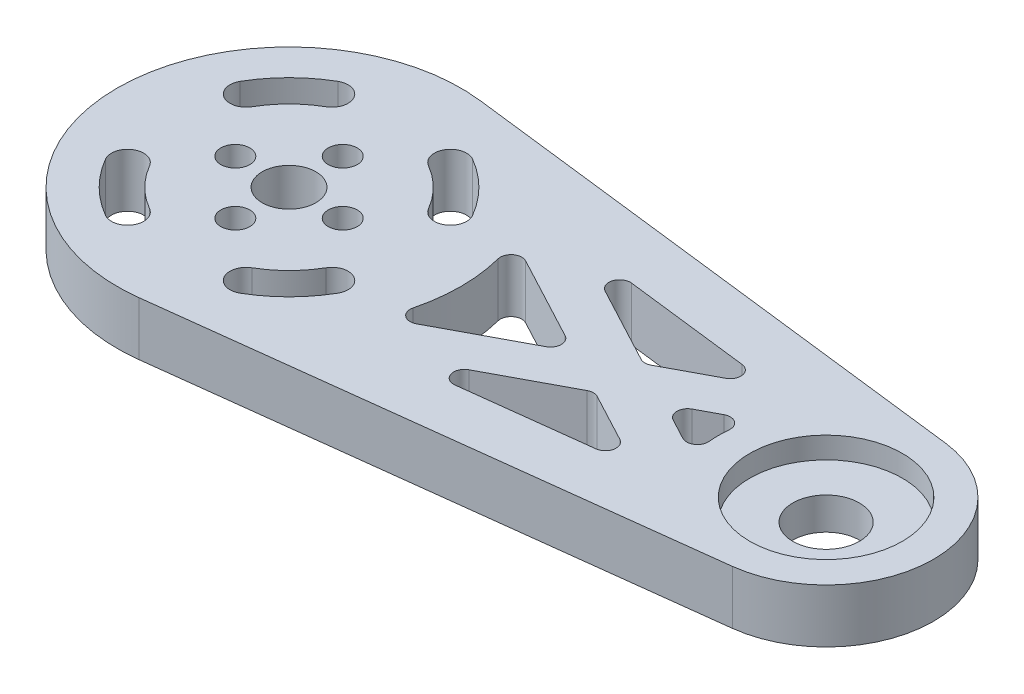
SolidWorks part; units mm, degrees
material "三聚氰胺甲醛树脂"
ref_plane "前视基准面" through (0, 0, 0) normal (0, 0, 1) x (1, 0, 0)
ref_plane "上视基准面" through (0, 0, 0) normal (0, 1, 0) x (1, 0, 0)
ref_plane "右视基准面" through (0, 0, 0) normal (1, 0, 0) x (0, 0, -1)
sketch "草图1" plane through (0, 0, 0) normal (0, 1, 0) x (1, 0, 0)
  line L0 (0, 0) -> (-5.9584, 0) construction
  line L1 (1.92, -15.8844) -> (51.2, -9.9277)
  line L2 (1.92, 15.8844) -> (51.2, 9.9277)
  line L3 (18.3565, 8.8613) -> (38.5355, 6.4222)
  line L4 (18.3565, -8.8613) -> (38.5355, -6.4222)
  line L5 (12.855, 9.5262) -> (42.0023, -6.0031) construction
  line L6 (12.855, -9.5262) -> (42.0023, 6.0031) construction
  line L7 (14.7223, 6.2652) -> (26.4816, 0)
  line L8 (18.3565, 8.8613) -> (30.735, 2.2662)
  line L9 (14.7223, -6.2652) -> (26.4816, 0)
  line L10 (18.3565, -8.8613) -> (30.735, -2.2662)
  line L11 (30.735, 2.2662) -> (38.5355, 6.4222)
  line L12 (34.9884, 0) -> (40.4294, -2.8989)
  line L13 (34.9884, 0) -> (40.4294, 2.8989)
  line L14 (30.735, -2.2662) -> (38.5355, -6.4222)
  line L15 (7.7782, -7.7782) -> (0, 0) construction
  circle A0 centre (0, 0) radius 5 construction
  circle A1 centre (-5, 0) radius 1.35
  circle A2 centre (0, 5) radius 1.35
  circle A3 centre (5, 0) radius 1.35
  circle A4 centre (0, -5) radius 1.35
  arc A5 (1.92, 15.8844) -> (1.92, -15.8844) centre (0, 0) ccw
  circle A6 centre (0, 0) radius 2.5
  arc A7 (40.4294, 2.8989) -> (40.4294, -2.8989) centre (50, 0) ccw
  circle A8 centre (50, 0) radius 3.1
  circle A9 centre (50, 0) radius 7.1
  arc A10 (14.7223, -6.2652) -> (14.7223, 6.2652) centre (0, 0) ccw
  circle A11 centre (0, 0) radius 16 construction
  arc A12 (51.2, -9.9277) -> (51.2, 9.9277) centre (50, 0) ccw
  circle A13 centre (50, 0) radius 10 construction
  arc A14 (5.5166, -9.5166) -> (9.5166, -5.5166) centre (0, 0) ccw construction
  arc A15 (6.2689, -10.8144) -> (10.8144, -6.2689) centre (0, 0) ccw
  arc A16 (4.7644, -8.2189) -> (8.2189, -4.7644) centre (0, 0) ccw
  arc A17 (4.7644, -8.2189) -> (6.2689, -10.8144) centre (5.5166, -9.5166) ccw
  arc A18 (10.8144, -6.2689) -> (8.2189, -4.7644) centre (9.5166, -5.5166) ccw
  arc A19 (-9.5166, -5.5166) -> (-5.5166, -9.5166) centre (0, 0) ccw construction
  arc A20 (-10.8144, -6.2689) -> (-6.2689, -10.8144) centre (0, 0) ccw
  arc A21 (-8.2189, -4.7644) -> (-4.7644, -8.2189) centre (0, 0) ccw
  arc A22 (-8.2189, -4.7644) -> (-10.8144, -6.2689) centre (-9.5166, -5.5166) ccw
  arc A23 (-6.2689, -10.8144) -> (-4.7644, -8.2189) centre (-5.5166, -9.5166) ccw
  arc A24 (-5.5166, 9.5166) -> (-9.5166, 5.5166) centre (0, 0) ccw construction
  arc A25 (-6.2689, 10.8144) -> (-10.8144, 6.2689) centre (0, 0) ccw
  arc A26 (-4.7644, 8.2189) -> (-8.2189, 4.7644) centre (0, 0) ccw
  arc A27 (-4.7644, 8.2189) -> (-6.2689, 10.8144) centre (-5.5166, 9.5166) ccw
  arc A28 (-10.8144, 6.2689) -> (-8.2189, 4.7644) centre (-9.5166, 5.5166) ccw
  arc A29 (9.5166, 5.5166) -> (5.5166, 9.5166) centre (0, 0) ccw construction
  arc A30 (10.8144, 6.2689) -> (6.2689, 10.8144) centre (0, 0) ccw
  arc A31 (8.2189, 4.7644) -> (4.7644, 8.2189) centre (0, 0) ccw
  arc A32 (8.2189, 4.7644) -> (10.8144, 6.2689) centre (9.5166, 5.5166) ccw
  arc A33 (6.2689, 10.8144) -> (4.7644, 8.2189) centre (5.5166, 9.5166) ccw
  point P15 (0, 0)
  point P36 (7.7782, -7.7782)
  point P53 (-7.7782, -7.7782)
  point P60 (-7.7782, 7.7782)
  point P67 (7.7782, 7.7782)
  point P72 (0, 0)
  dimension "D1" = 10
  dimension "D2" = 2.7
  dimension "D4" = 20
  dimension "D5" = 32
  dimension "D6" = 5
  dimension "D7" = 6.2
  dimension "D8" = 14.2
  dimension "D15" = 11
  dimension "D16" = 1.5
  dimension "D3" = 50
  dimension "D9" = 5
  dimension "D10" = 5
  dimension "D11" = 2
  dimension "D12" = 2
  dimension "D13" = 2
  dimension "D14" = 2
  dimension "D17" = 4
  dimension "D18" = 45
  dimension "D19" = 4
extrude "凸台-拉伸1" add sketch "草图1" along normal blind 5 contours L1 A7 L2 A5 A9 A1 A2 A3 A4 A6 region at (-15.1754, 0, 0)
extrude "凸台-拉伸2" add sketch "草图1<3>" along normal blind 3 contours A9 A8 region at (43.1008, 0, 0)
sketch "草图1<3>" plane through (0, 0, 0) normal (0, 1, 0) x (1, 0, 0) same geometry as "草图1"
fillet "圆角1" radius 1 3 edges at (34.9884, 2.5, 0) (40.4294, 2.5, -2.8989) (40.4294, 2.5, 2.8989)
fillet "圆角2" radius 1 3 edges at (30.735, 2.5, 2.2662) (18.3565, 2.5, 8.8613) (38.5355, 2.5, 6.4222)
fillet "圆角3" radius 1 3 edges at (18.3565, 2.5, -8.8613) (30.735, 2.5, -2.2662) (38.5355, 2.5, -6.4222)
fillet "圆角4" radius 1 3 edges at (14.7223, 2.5, -6.2652) (26.4816, 2.5, 0) (14.7223, 2.5, 6.2652)
sketch "草图2" plane through (0, 5, 0) normal (0, 1, 0) x (1, 0, 0)
  line L0 (1.62, -13.4024) -> (50.9, -7.4458)
  line L1 (50.9, 7.4458) -> (1.62, 13.4024)
  line L2 (1.92, -15.8844) -> (51.2, -9.9277)
  line L3 (51.2, 9.9277) -> (1.92, 15.8844)
  line L4 (1.92, -15.8844) -> (51.2, -9.9277)
  line L5 (51.2, 9.9277) -> (1.92, 15.8844)
  arc A0 (1.62, 13.4024) -> (1.62, -13.4024) centre (0, 0) ccw
  arc A1 (50.9, -7.4458) -> (50.9, 7.4458) centre (50, 0) ccw
  arc A2 (51.2, -9.9277) -> (51.2, 9.9277) centre (50, 0) ccw
  arc A3 (1.92, 15.8844) -> (1.92, -15.8844) centre (0, 0) ccw
  arc A4 (51.2, -9.9277) -> (51.2, 9.9277) centre (50, 0) ccw
  arc A5 (1.92, 15.8844) -> (1.92, -15.8844) centre (0, 0) ccw
  dimension "D1" = 0
  dimension "D2" = 2.5
